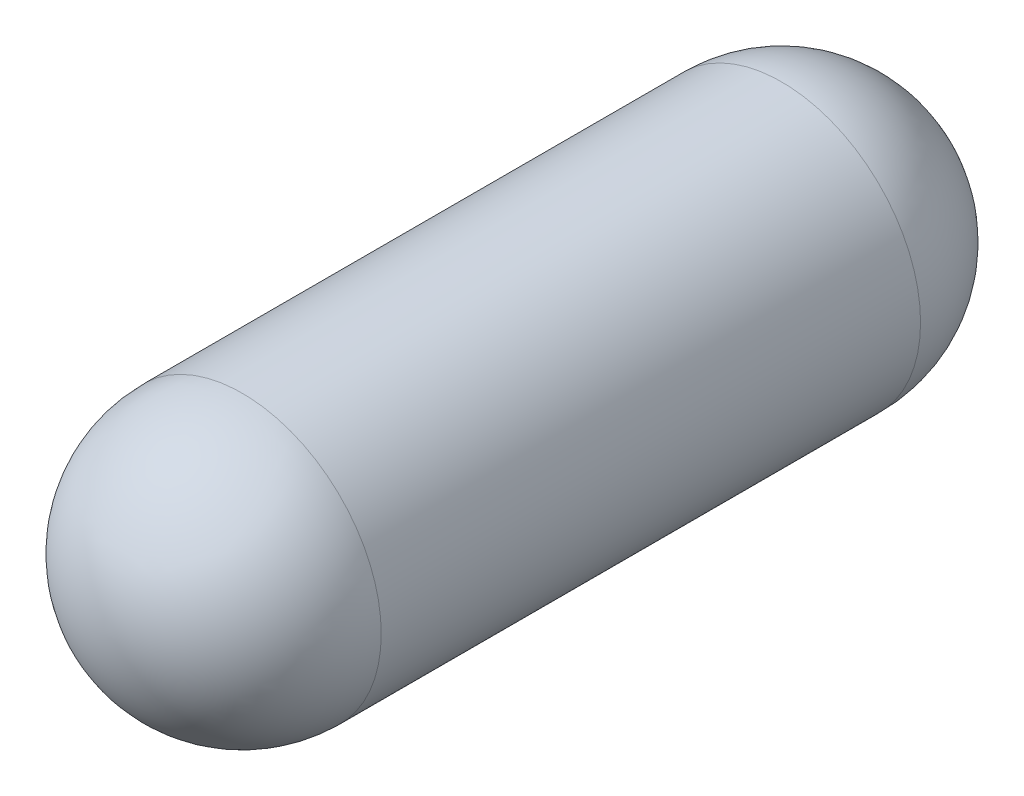
SolidWorks part; units mm, degrees
ref_plane "Front Plane" through (0, 0, 0) normal (0, 0, 1) x (1, 0, 0)
ref_plane "Top Plane" through (0, 0, 0) normal (0, 1, 0) x (1, 0, 0)
ref_plane "Right Plane" through (0, 0, 0) normal (1, 0, 0) x (0, 0, -1)
sketch "Sketch2" plane through (0, 0, 0) normal (0, 0, 1) x (1, 0, 0)
  line L0 (-6.3689, 0) -> (6.3689, 0) construction
  line L1 (-8.5, 0) -> (8.5, 0)
  circle A0 centre (0, 0) radius 8.5
  point P5 (0, 0)
  dimension "D1" = 17
extrude "Boss-Extrude1" add sketch "Sketch2" along normal blind 25 and the other way blind 25 contours A0
fillet "Fillet1" radius 8.5 2 edges at (8.5, 0, -25) (8.5, 0, 25)
